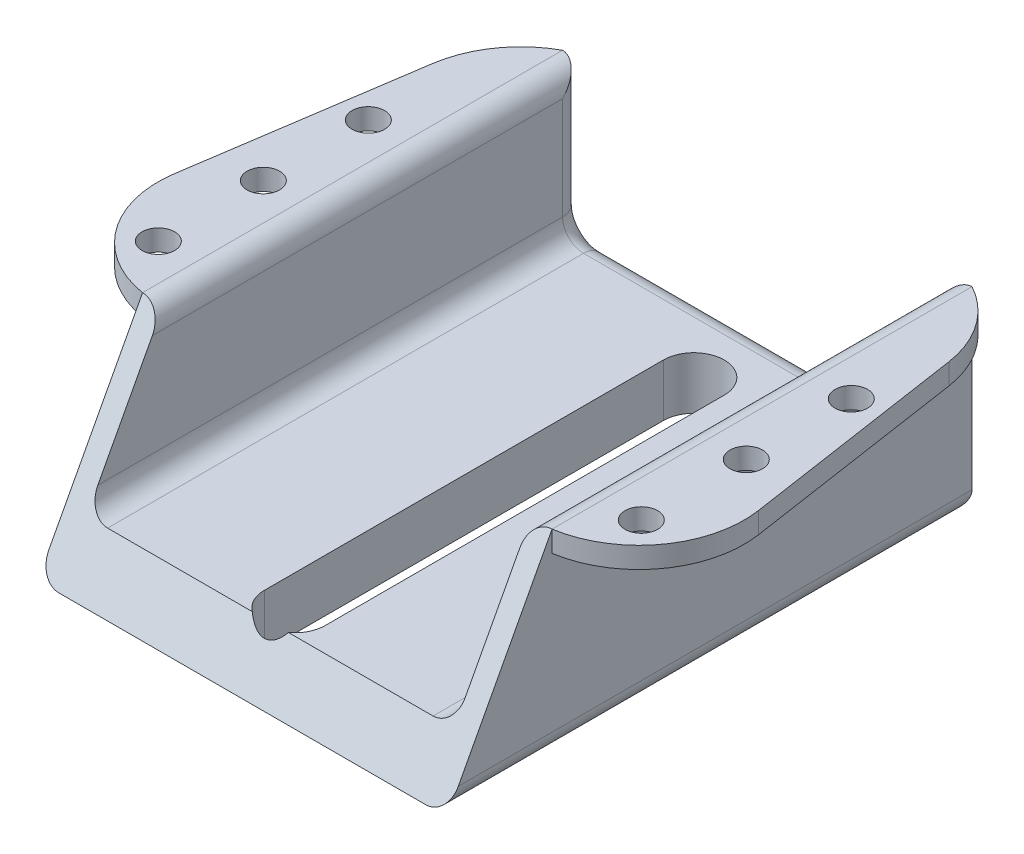
SolidWorks part; units mm, degrees
ref_plane "Front Plane" through (0, 0, 0) normal (0, 0, 1) x (1, 0, 0)
ref_plane "Top Plane" through (0, 0, 0) normal (0, 1, 0) x (1, 0, 0)
ref_plane "Right Plane" through (0, 0, 0) normal (1, 0, 0) x (0, 0, -1)
sketch "Sketch2" plane through (0, 0, 0) normal (0, 1, 0) x (1, 0, 0)
  line L1 (-17.5, -25) -> (17.5, -25)
  line L2 (-17.5, -25) -> (-17.5, 25)
  line L3 (-17.5, 25) -> (17.5, 25)
  line L4 (17.5, -25) -> (17.5, 25)
  line L5 (-17.5, -25) -> (17.5, 25) construction
  line L6 (-17.5, 25) -> (17.5, -25) construction
  circle A0 centre (0, 0) radius 7 construction
  point P0 (0, 0)
  point P16 (0, 0)
  dimension "D1" = 14
  dimension "D4" = 50
  dimension "D5" = 35
extrude "Boss-Extrude1" add sketch "Sketch2" along normal blind 5
sketch "Sketch3" plane through (17.5, 0, 0) normal (1, 0, 0) x (0, 0, -1)
  line L0 (-25, 0) -> (-15, 18.75)
  line L1 (-15, 18.75) -> (25, 18.75)
  line L3 (-25, 0) -> (25, 0)
  line L4 (25, 18.75) -> (25, 0)
  dimension "D1" = 18.75
  dimension "D2" = 40
extrude "Boss-Extrude2" add sketch "Sketch3" along normal blind 2
mirror "Mirror1" about plane through (0, 0, 0) normal (1, 0, 0) of "Boss-Extrude2"
sketch "Sketch4" plane through (0, 18.75, 0) normal (0, 1, 0) x (1, 0, 0)
  line L0 (-19.5, -15) -> (-29.5, -15)
  line L4 (-19.5, 25) -> (-19.5, -15)
  line L6 (-23, -10) -> (-23, -15) construction
  line L7 (-19.5, 25) -> (-23.5, 25)
  line L8 (-23.5, 25) -> (-29.5, -15)
  line L9 (-19.5, 25) -> (-17.5, 25) construction
  line L10 (-23, -10) -> (-23, 0) construction
  line L12 (-19.5, 25) -> (-19.5, -15) construction
  line L13 (-23, 0) -> (-23, 10) construction
  circle A1 centre (-23, -10) radius 1.55
  circle A2 centre (-23, 0) radius 1.55
  circle A3 centre (-23, 10) radius 1.55
  point P12 (-19.5, -20)
  dimension "D2" = 3.1
  dimension "D1" = 10
  dimension "D4" = 5
  dimension "D5" = 4
  dimension "D6" = 10
  dimension "D7" = 3.5
  dimension "D8" = 10
extrude "Boss-Extrude3" add sketch "Sketch4" against normal blind 2
fillet "Fillet1" radius 2 8 edges at (-17.5, 18.75, -5) (17.5, 18.75, -5) (0, 5, -25) (0, 0, -25) (17.5, 5, -1.3333) (-17.5, 5, -1.3333) (-19.5, 0, 0) (19.5, 0, 0)
mirror "Mirror2" about plane through (0, 0, 0) normal (1, 0, 0) of "Boss-Extrude3"
fillet "Fillet2" radius 10 4 edges at (-29.5, 17.75, 15) (29.5, 17.75, 15) (-23.5, 17.75, -25) (23.5, 17.75, -25)
sketch "Sketch5" plane through (0, 5, 0) normal (0, 1, 0) x (1, 0, 0)
  line L0 (0, 23) -> (0, -25) construction
  line L1 (15.5, 23) -> (-15.5, 23) construction
  line L2 (-17.5, -25) -> (17.5, -25) construction
  line L3 (0, 18) -> (0, -20) construction
  line L4 (2.9, 18) -> (2.9, -20)
  line L5 (-2.9, 18) -> (-2.9, -20)
  arc A0 (2.9, 18) -> (-2.9, 18) centre (0, 18) ccw
  arc A1 (-2.9, -20) -> (2.9, -20) centre (0, -20) ccw
  point P8 (0, -1)
  point P13 (0, 0)
  point P14 (0, -1)
  point P15 (0, 0)
  dimension "D1" = 38
  dimension "D2" = 5.8
extrude "Cut-Extrude1" cut sketch "Sketch5" against normal through all
sketch "Sketch6" plane through (-17.5, 0, 0) normal (-1, 0, 0) x (0, 0, 1)
  line L0 (25, 5) -> (22.3333, 5)
  line L1 (22.3333, 5) -> (25, 0)
  line L2 (25, 5) -> (25, 0) construction
  line L3 (22.3333, 5) -> (25, 0) construction
  line L4 (25, 0) -> (25, 5)
extrude "Cut-Extrude2" cut sketch "Sketch6" against normal through all
